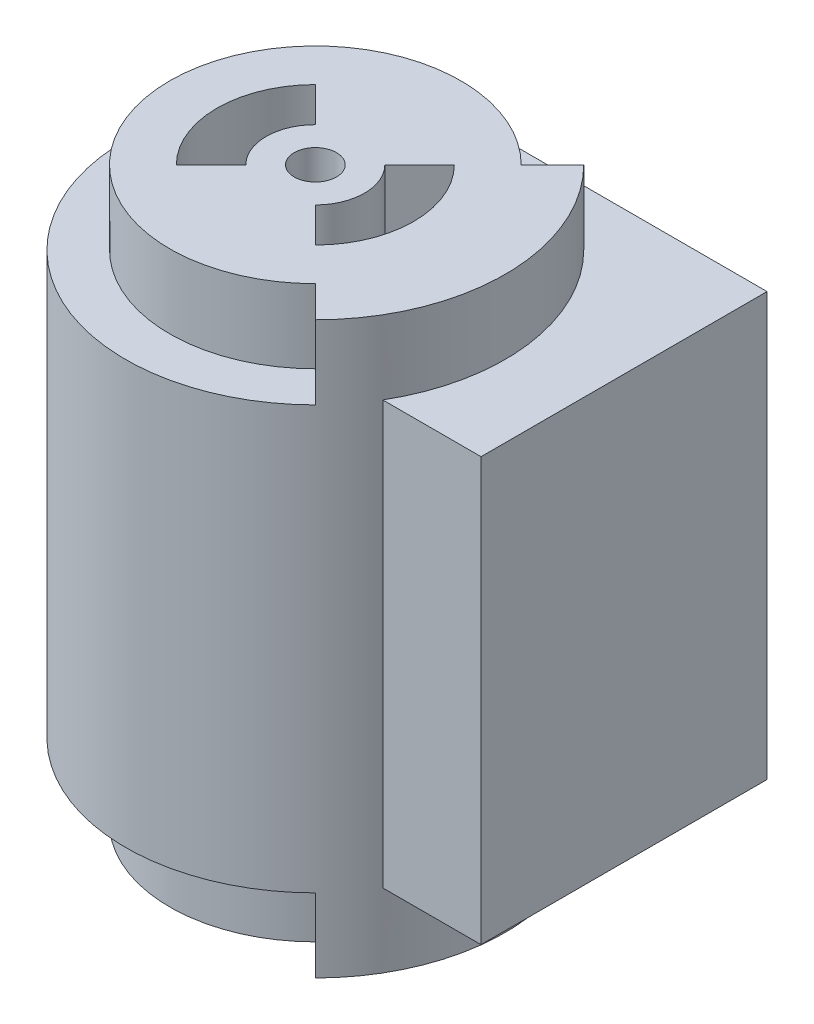
SolidWorks part; units mm, degrees
ref_plane "Front Plane" through (0, 0, 0) normal (0, 0, 1) x (1, 0, 0)
ref_plane "Top Plane" through (0, 0, 0) normal (0, 1, 0) x (1, 0, 0)
ref_plane "Right Plane" through (0, 0, 0) normal (1, 0, 0) x (0, 0, -1)
sketch "Sketch1" plane through (0, 0, 0) normal (0, 1, 0) x (1, 0, 0)
  line L0 (0, 38.625) -> (53.2973, 38.625)
  line L1 (53.2973, 38.625) -> (53.2973, -19.575)
  line L2 (53.2973, -19.575) -> (33.2973, -19.575)
  line L3 (0, 60.3307) -> (0, -56.6529) construction
  arc A0 (0, 38.625) -> (33.2973, -19.575) centre (0, 0) ccw
  dimension "D1" = 20
  dimension "D2" = 38.625
  dimension "D7" = 58.2
extrude "Boss-Extrude1" add sketch "Sketch1" along normal blind 43
sketch "Sketch4" plane through (0, 0, 0) normal (0, -1, 0) x (1, 0, 0)
  line L0 (-38.625, 0) -> (53.2973, 0) construction
  line L1 (53.2973, 19.575) -> (53.2973, -38.625) construction
  line L2 (20.948, 20.948) -> (27.312, 27.312)
  line L3 (20.948, -20.948) -> (27.312, -27.312)
  line L4 (20.948, -20.948) -> (0, 0) construction
  line L5 (0, 0) -> (20.948, 20.948) construction
  arc A0 (33.2973, 19.575) -> (0, -38.625) centre (0, 0) ccw construction
  arc A1 (20.948, 20.948) -> (20.948, -20.948) centre (0, 0) ccw
  arc A4 (27.312, -27.312) -> (27.312, 27.312) centre (0, 0) ccw
  dimension "D1" = 45
  dimension "D2" = 45
  dimension "D3" = 9
extrude "Boss-Extrude2" add sketch "Sketch4" along normal blind 15
sketch "Sketch6" plane through (0, -15, 0) normal (0, -1, 0) x (1, 0, 0)
  line L0 (0, -38.625) -> (0, 38.625) construction
  line L1 (38.625, 0) -> (-38.625, 0) construction
  line L2 (7.0711, 7.0711) -> (14.1421, 14.1421)
  line L3 (7.0711, -7.0711) -> (14.1421, -14.1421)
  line L4 (0, 0) -> (7.0711, 7.0711) construction
  line L5 (7.0711, -7.0711) -> (0, 0) construction
  line L6 (-7.0711, -7.0711) -> (-14.1421, -14.1421)
  line L7 (-7.0711, 7.0711) -> (-14.1421, 14.1421)
  circle A0 centre (0, 0) radius 4.3
  arc A1 (27.312, 27.312) -> (0, -38.625) centre (0, 0) ccw construction
  arc A2 (27.312, -27.312) -> (27.312, 27.312) centre (0, 0) ccw construction
  arc A3 (7.0711, 7.0711) -> (7.0711, -7.0711) centre (0, 0) cw
  arc A4 (14.1421, -14.1421) -> (14.1421, 14.1421) centre (0, 0) ccw
  arc A5 (-14.1421, -14.1421) -> (-14.1421, 14.1421) centre (0, 0) cw
  arc A6 (-7.0711, 7.0711) -> (-7.0711, -7.0711) centre (0, 0) ccw
  dimension "D1" = 8.6
  dimension "D3" = 10
  dimension "D4" = 10
  dimension "D2" = 45
  dimension "D5" = 45
extrude "Cut-Extrude4" cut sketch "Sketch6" against normal through all both and the other way through all
mirror "Mirror1" about plane through (0, 43, 0) normal (0, 1, 0) of "Cut-Extrude4", "Boss-Extrude2", "Boss-Extrude1"
